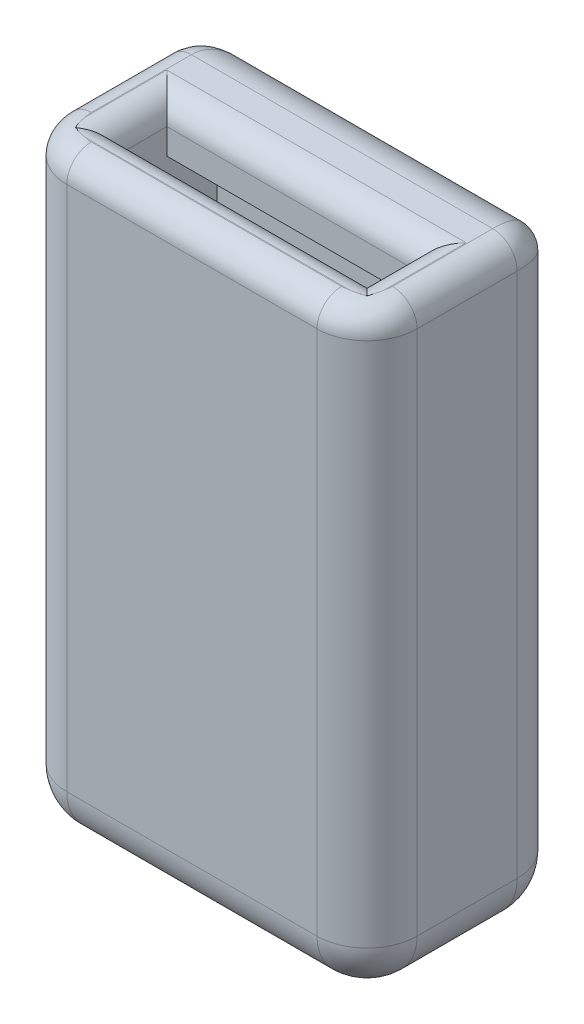
SolidWorks part; units mm, degrees
material "POLYURETHANE (11671)"
ref_plane "Front Plane" through (0, 0, 0) normal (0, 0, 1) x (1, 0, 0)
ref_plane "Top Plane" through (0, 0, 0) normal (0, 1, 0) x (1, 0, 0)
ref_plane "Right Plane" through (0, 0, 0) normal (1, 0, 0) x (0, 0, -1)
sketch "Sketch2" plane through (0, 0, 0) normal (0, 1, 0) x (1, 0, 0)
  line L0 (-6.35, 2.54) -> (-6.35, 5.08) construction
  line L1 (6.35, 2.54) -> (-6.35, 2.54)
  line L2 (6.35, 2.54) -> (6.35, -2.54)
  line L3 (6.35, -2.54) -> (-6.35, -2.54)
  line L4 (-6.35, 2.54) -> (-6.35, -2.54)
  line L5 (8.89, 5.08) -> (-8.89, 5.08)
  line L6 (8.89, 5.08) -> (8.89, -5.08)
  line L7 (8.89, -5.08) -> (-8.89, -5.08)
  line L8 (-8.89, 5.08) -> (-8.89, -5.08)
  line L9 (-6.35, 2.54) -> (-8.89, 2.54) construction
  point P8 (0, 5.08)
  point P9 (0, 2.54)
  point P11 (-6.35, 0)
  point P12 (-8.89, 0)
  dimension "D1" = 12.7
  dimension "D2" = 5.08
  dimension "D3" = 2.54
extrude "Boss-Extrude1" add sketch "Sketch2" along normal mid plane 30.48
sketch "Sketch3" plane through (0, -15.24, 0) normal (0, -1, 0) x (1, 0, 0)
  line L1 (-6.35, 2.54) -> (6.35, 2.54)
  line L2 (-6.35, 2.54) -> (-6.35, -2.54)
  line L3 (-6.35, -2.54) -> (6.35, -2.54)
  line L4 (6.35, 2.54) -> (6.35, -2.54)
extrude "Boss-Extrude2" add sketch "Sketch3" against normal blind 2.54
sketch "Sketch4" plane through (0, 15.24, 0) normal (0, 1, 0) x (1, 0, 0)
  line L0 (6.35, -2.54) -> (6.35, 2.54) construction
  line L1 (-6.35, 2.54) -> (6.35, 2.54)
  line L2 (-6.35, 2.54) -> (-6.35, 0)
  line L3 (-6.35, 0) -> (6.35, 0)
  line L4 (6.35, 2.54) -> (6.35, 0)
  line L5 (6.35, -2.54) -> (-6.35, -2.54) construction
  dimension "D1" = 2.54
extrude "Boss-Extrude3" add sketch "Sketch4" against normal blind 2.54
fillet "Fillet1" radius 2.54 9 edges at (-8.89, 0, -5.08) (-8.89, 0, 5.08) (8.89, 0, -5.08) (8.89, 0, 5.08) (0, 15.24, -5.08) (-8.89, -15.24, 0) (8.89, -15.24, 0) (0, -15.24, 5.08) (0, -15.24, -5.08)
fillet "Fillet2" radius 1.2446 11 edges at (-8.1461, 14.4961, -4.3361) (-8.89, 15.24, 0) (-8.1461, 15.24, 4.3361) (0, 15.24, 5.08) (8.1461, 15.24, 4.3361) (8.1461, 14.4961, -4.3361) (-6.35, 15.24, 1.27) (0, 15.24, 2.54) (6.35, 15.24, 1.27) (0, 15.24, 0) (8.89, 15.24, 0)
